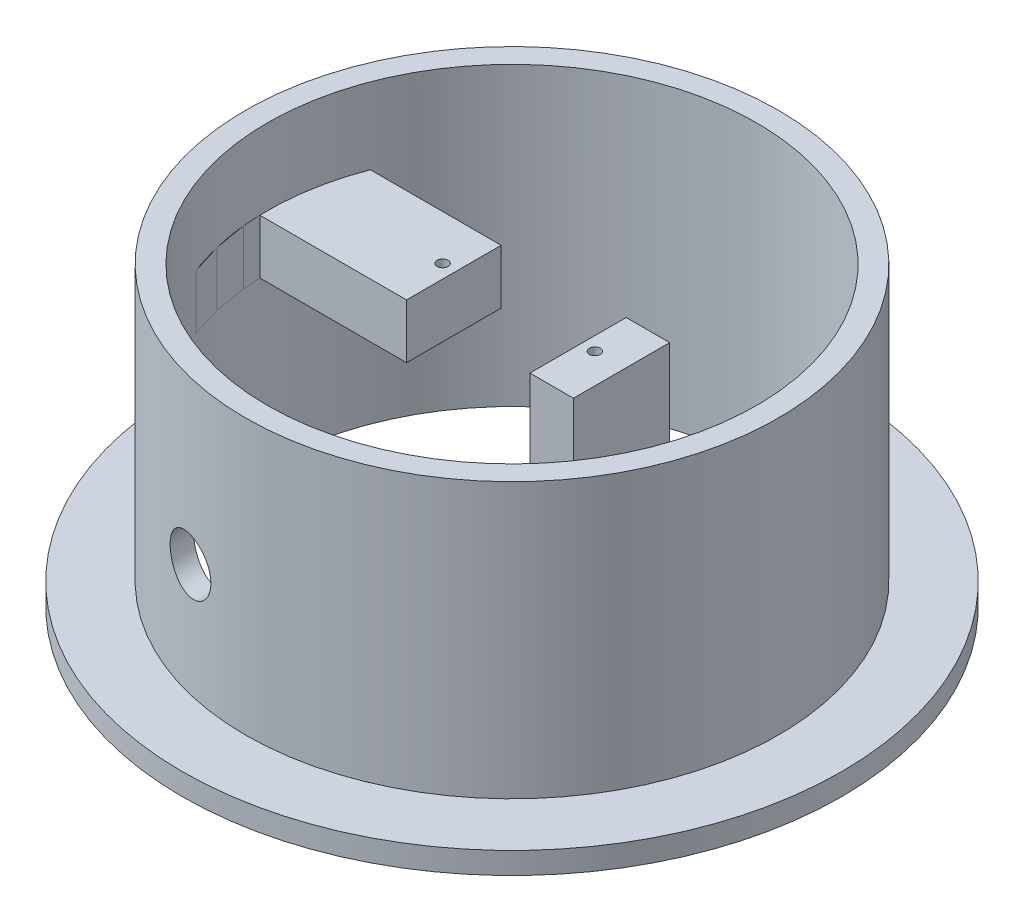
SolidWorks part; units mm, degrees
ref_plane "Front Plane" through (0, 0, 0) normal (0, 0, 1) x (1, 0, 0)
ref_plane "Top Plane" through (0, 0, 0) normal (0, 1, 0) x (1, 0, 0)
ref_plane "Right Plane" through (0, 0, 0) normal (1, 0, 0) x (0, 0, -1)
sketch "Sketch1" plane through (0, 0, 0) normal (0, 1, 0) x (1, 0, 0)
  circle A0 centre (0, 0) radius 60.625
  circle A1 centre (0, 0) radius 45
  dimension "D1" = 121.25
  dimension "D2" = 90
extrude "Boss-Extrude1" add sketch "Sketch1" along normal blind 4
sketch "Sketch2" plane through (0, 4, 0) normal (0, 1, 0) x (1, 0, 0)
  circle A0 centre (0, 0) radius 45 construction
  circle A1 centre (0, 0) radius 45
  circle A2 centre (0, 0) radius 49
  dimension "D1" = 4
extrude "Boss-Extrude2" add sketch "Sketch2" along normal blind 50.5
ref_plane "Plane1" through (0, 34.5, 0) normal (0, 1, 0) x (1, 0, 0)
sketch "Sketch4" plane through (0, 0, 0) normal (0, 0, 1) x (1, 0, 0)
  line L0 (-60.625, 0) -> (60.625, 0) construction
  line L1 (5, 40.5) -> (13, 40.5)
  line L2 (5, 40.5) -> (5, 0)
  line L3 (5, 0) -> (13, 0)
  line L4 (13, 40.5) -> (13, 0)
  line L5 (49, 54.5) -> (-49, 54.5) construction
  line L6 (-45, 54.5) -> (-45, 4)
  line L7 (-18, 40.5) -> (-45, 40.5)
  line L8 (-18, 40.5) -> (-18, 30.5)
  line L9 (-18, 30.5) -> (-45, 30.5)
  line L10 (-45, 40.5) -> (-45, 30.5)
  line L11 (60.625, 4) -> (-60.625, 4) construction
  line L12 (-18, 30.5) -> (-45, 3.5)
  dimension "D1" = 5
  dimension "D2" = 8
  dimension "D3" = 14
  dimension "D4" = 23
  dimension "D5" = 27
  dimension "D6" = 10
  dimension "D7" = 45
  dimension "D8" = 14
extrude "Boss-Extrude4" add sketch "Sketch4" along normal mid plane 32 contours L9 L8 L7 L6 | L12 L9 L6 | L1 L4 L3 L2 region at (-31.5, 35.5, 0)
sketch "Sketch5" plane through (0, 0, 0.8324) normal (0, -1, 0) x (1, 0, 0)
  line L0 (0.9227, 14.5796) -> (36.1058, 30.1379)
  line L1 (0.9227, -16.0291) -> (36.6512, -32.9046)
  line L2 (0.9227, 14.5796) -> (0.9227, -16.0291)
  arc A1 (36.6512, -32.9046) -> (36.1058, 30.1379) centre (-2.8733, -1.7229) ccw
extrude "Boss-Extrude5" add sketch "Sketch5" against normal up to surface (4 mm away) contours L0 A1 L1 L2 up to face at (0, 4, 60.625)
sketch "Sketch6" plane through (0, 0, 0) normal (0, 0, 1) x (1, 0, 0)
  circle A0 centre (-11.8474, 24.4856) radius 5
extrude "Cut-Extrude2" cut sketch "Sketch6" along normal blind 52 contours A0
sketch "Sketch7" plane through (0, 40.5, 0) normal (0, 1, 0) x (1, 0, 0)
  line L0 (-18, -16) -> (-18, 16) construction
  line L1 (5, -16) -> (5, 16) construction
  circle A0 centre (-20.5, 7.7399) radius 1
  circle A1 centre (7.5, 7.7399) radius 1
  dimension "D1" = 2.5
  dimension "D2" = 2.5
extrude "Cut-Extrude3" cut sketch "Sketch7" against normal blind 4.5
sketch "Sketch8" plane through (0, 40.5, 0.701) normal (0, 1, 0) x (1, 0, 0)
  line L1 (5, -1) -> (13, -1)
  line L2 (5, -1) -> (5, -16)
  line L3 (5, -16) -> (13, -16)
  line L4 (13, -1) -> (13, -16)
  dimension "D1" = 8
  dimension "D2" = 15
sketch "Sketch9" plane through (0, 40.5, 0.701) normal (0, 1, 0) x (1, 0, 0)
  line L1 (-41.34, -0.6916) -> (-16.34, -0.6916)
  line L2 (-41.34, -0.6916) -> (-41.34, -16.5689)
  line L3 (-41.34, -16.5689) -> (-16.34, -16.5689)
  line L4 (-16.34, -0.6916) -> (-16.34, -16.5689)
  dimension "D1" = 25
  dimension "D2" = 15.8773
extrude "Cut-Extrude5" cut sketch "Sketch9" against normal blind 35
sketch "Sketch11" plane through (0, 4, 0) normal (0, 1, 0) x (1, 0, 0)
  line L0 (16.2655, 12.7324) -> (16.2655, -6.5497)
  line L1 (16.2655, -6.5497) -> (5.715, -6.5497)
  line L2 (5.715, -6.5497) -> (5.715, -11.643)
  line L3 (5.715, -11.643) -> (30.818, -22.5574)
  line L4 (16.2655, 12.7324) -> (32.152, 20.615)
  arc A0 (32.152, 20.615) -> (30.818, -22.5574) centre (5.8984, -0.1806) cw
extrude "Cut-Extrude6" cut sketch "Sketch11" against normal through all
extrude "Cut-Extrude7" cut sketch "Sketch8" against normal blind 36.5
sketch "Sketch12" plane through (0, 40.5, 0) normal (0, 1, 0) x (1, 0, 0)
  line L0 (-41.34, -1.3926) -> (-41.34, -16)
  line L1 (-41.34, -16) -> (-42.0595, -16)
  line L2 (-41.34, -16) -> (-42.0595, -16) construction
  line L3 (-42.0595, -16) -> (-43.7701, -10.449)
  line L4 (-43.7701, -10.449) -> (-44.7608, -4.6338)
  line L5 (-44.7608, -4.6338) -> (-44.9784, -1.3926)
  line L6 (-44.9784, -1.3926) -> (-41.34, -1.3926)
  circle A0 centre (0, 0) radius 45 construction
  arc A1 (-42.0595, 16) -> (-42.0595, -16) centre (0, 0) ccw construction
split "Split1" trim tools "Sketch12" bodies to split 135 resulting bodies 136 137
delete or keep bodies "Body-Delete/Keep 1" type delete bodies bodies 136
